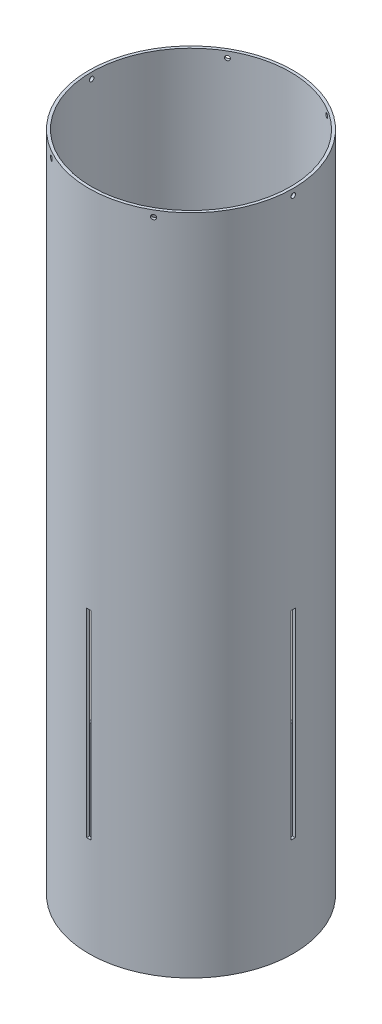
SolidWorks part; units mm, degrees
ref_plane "Front Plane" through (0, 0, 0) normal (0, 0, 1) x (1, 0, 0)
ref_plane "Top Plane" through (0, 0, 0) normal (0, 1, 0) x (1, 0, 0)
ref_plane "Right Plane" through (0, 0, 0) normal (1, 0, 0) x (0, 0, -1)
sketch "Sketch1" plane through (0, 0, 0) normal (0, 1, 0) x (1, 0, 0)
  circle A0 centre (0, 0) radius 76.2
  circle A1 centre (0, 0) radius 78.359
  dimension "D1" = 152.4
  dimension "D2" = 156.718
extrude "Boss-Extrude1" add sketch "Sketch1" along normal blind 508
ref_axis "Axis1" through (0, 508, 0) along (0, -1, 0)
sketch "Sketch2" plane through (0, 0, 0) normal (1, 0, 0) x (0, 0, -1)
  line L0 (0, 0) -> (0, 76.2)
  line L1 (1.5875, 76.2) -> (-1.5875, 76.2)
  line L2 (1.5875, 76.2) -> (1.5875, 228.6)
  line L3 (1.5875, 228.6) -> (-1.5875, 228.6)
  line L4 (-1.5875, 76.2) -> (-1.5875, 228.6)
  line L5 (1.5875, 76.2) -> (-1.5875, 228.6) construction
  line L6 (1.5875, 228.6) -> (-1.5875, 76.2) construction
  line L7 (78.359, 508) -> (-78.359, 508) construction
  line L8 (78.359, 508) -> (-78.359, 508)
  line L9 (0, 508) -> (0, 503.2375)
  circle A0 centre (0, 503.2375) radius 1.75
  point P0 (0, 152.4)
  dimension "D4" = 3.5
  dimension "D1" = 3.175
  dimension "D2" = 152.4
  dimension "D3" = 76.2
  dimension "D5" = 4.7625
extrude "Cut-Extrude1" cut sketch "Sketch2" against normal through all contours L4 L1 L2 L3 region at (0, 152.4, 0)
pattern_circular "CirPattern1" count 4 over 360 about axis through (0, 0, 0) along (0, 1, 0) of "Cut-Extrude1" reverse direction yes
extrude "Cut-Extrude2" cut sketch "Sketch2<3>" against normal through all contours A0 region at (0, 502.0351, 1.2024)
sketch "Sketch2<3>" plane through (0, 0, 0) normal (1, 0, 0) x (0, 0, -1) same geometry as "Sketch2"
pattern_circular "CirPattern2" count 6 over 360 about axis through (0, 508, 0) along (0, -1, 0) of "Cut-Extrude2"
equation "\"Aft_Lower_Length\"= 20in"
equation "\"D1@Boss-Extrude1\"=\"Aft_Lower_Length\""
equation "\"AB_Coupler_OD_Length\"= 2in"
equation "\"AB_Coupling_Section_Length\"= 0.375in"
equation "\"AB_Coupler_Length\"= \"AB_Coupler_OD_Length\" + \"AB_Coupling_Section_Length\" * 2"
equation "\"AB_Coupler_Num_Screws\"= 6"
equation "\"AB_Coupling_Screw_Diameter\"= 3.5mm"
equation "\"Aft_Upper_Length\"= \"Aft_Section_Length\" - \"Aft_Lower_Length\" - \"AB_Coupler_OD_Length\""
equation "\"Aft_Section_Length\"= 40in"
equation "\"D4@Sketch2\"=\"AB_Coupling_Screw_Diameter\""
equation "\"D5@Sketch2\"=\"AB_Coupling_Section_Length\"/2"
equation "\"D1@CirPattern2\"=\"AB_Coupler_Num_Screws\""
